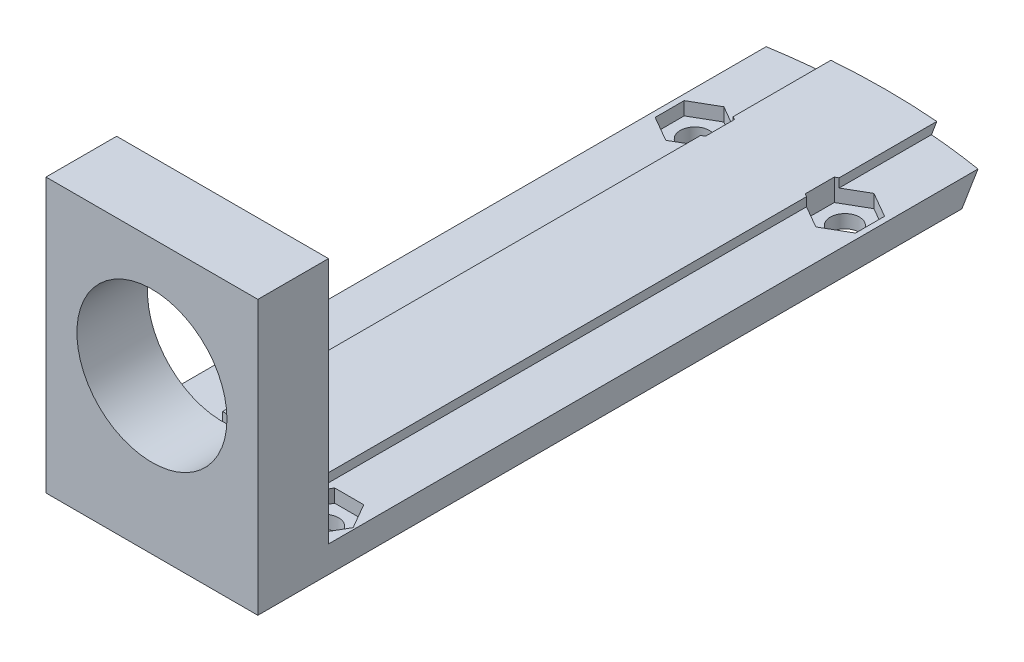
SolidWorks part; units mm, degrees
ref_plane "Front Plane" through (0, 0, 0) normal (0, 0, 1) x (1, 0, 0)
ref_plane "Top Plane" through (0, 0, 0) normal (0, 1, 0) x (1, 0, 0)
ref_plane "Right Plane" through (0, 0, 0) normal (1, 0, 0) x (0, 0, -1)
sketch "Sketch1" plane through (0, 0, 0) normal (0, 1, 0) x (1, 0, 0)
  line L1 (0, 0) -> (24, 0)
  line L2 (0, 0) -> (0, 81.5022)
  line L3 (0, 81.5022) -> (24, 81.5022)
  line L4 (24, 0) -> (24, 81.5022)
  dimension "D1" = 24
extrude "Boss-Extrude1" add sketch "Sketch1" along normal blind 3
sketch "Sketch2" plane through (0, 0, 0) normal (0, 1, 0) x (1, 0, 0)
  line L0 (0, 0) -> (24, 0) construction
  circle A0 centre (3.5, 3) radius 1.65
  circle A1 centre (12, 3) radius 1.65
  circle A2 centre (20.5, 3) radius 1.65
  circle A6 centre (3.5, 62) radius 1.65
  circle A8 centre (20.5, 62) radius 1.65
  circle A9 centre (12, 32.5) radius 1.65 [skipped]
  circle A10 centre (3.5, 32.5) radius 1.65 [skipped]
  circle A11 centre (20.5, 32.5) radius 1.65 [skipped]
  circle A12 centre (12, 62) radius 1.65 [skipped]
  point P9 (12, 0)
  dimension "D1" = 3.3
  dimension "D2" = 3
  dimension "D3" = 8.5
  dimension "D4" = 8.5
  dimension "D5" = 3
  dimension "D6" = 59
extrude "Cut-Extrude1" cut sketch "Sketch2" along normal through all
sketch "Sketch3" plane through (0, 0, 0) normal (0, 0, 1) x (1, 0, 0)
  line L0 (0, 3) -> (24, 3) construction
  line L1 (6, 3) -> (18, 3)
  line L2 (6, 3) -> (6, 4)
  line L3 (6, 4) -> (18, 4)
  line L4 (18, 3) -> (18, 4)
  line L5 (77.5014, 4) -> (-53.5014, 4) construction
  point P11 (12, 3)
  dimension "D1" = 12
  dimension "D2" = 12
extrude "Boss-Extrude2" add sketch "Sketch3" against normal up to surface (81.5022 mm away) from offset 6 up to face at (12, 1.5, -81.5022) offset against normal yes
ref_plane "Plane1" through (12, 0, 0) normal (-1, 0, 0) x (0, 0, 1)
sketch "Sketch4" plane through (12, 0, 0) normal (1, 0, 0) x (0, 0, -1)
  line L0 (94.4965, 36.2415) -> (19.4137, -88.8964)
  line L1 (19.4137, -88.8964) -> (139.5903, -88.8964)
  line L2 (139.5903, -88.8964) -> (139.5903, 36.2415)
  line L3 (139.5903, 36.2415) -> (94.4965, 36.2415)
  line L4 (73, -6) -> (79, 4) construction
  line L6 (0, 0) -> (0, 3) construction
  dimension "D1" = 3.3
revolve "Cut-Revolve1" cut sketch "Sketch4" angle 360 about L6
sketch "Sketch5" plane through (0, 3, 0) normal (0, 1, 0) x (1, 0, 0)
  line L0 (18, 74.3097) -> (18, 6) construction
  line L1 (15.2909, 3) -> (13.6454, 5.85)
  line L2 (13.6454, 5.85) -> (10.3546, 5.85)
  line L3 (10.3546, 5.85) -> (8.7091, 3)
  line L4 (8.7091, 3) -> (10.3546, 0.15)
  line L5 (10.3546, 0.15) -> (13.6454, 0.15)
  line L6 (13.6454, 0.15) -> (15.2909, 3)
  line L7 (23.7909, 3) -> (22.1454, 5.85)
  line L8 (22.1454, 5.85) -> (18.8546, 5.85)
  line L9 (18.8546, 5.85) -> (17.2091, 3)
  line L10 (17.2091, 3) -> (18.8546, 0.15)
  line L11 (18.8546, 0.15) -> (22.1454, 0.15)
  line L12 (22.1454, 0.15) -> (23.7909, 3)
  line L13 (6.7909, 3) -> (5.1454, 5.85)
  line L14 (5.1454, 5.85) -> (1.8546, 5.85)
  line L15 (1.8546, 5.85) -> (0.2091, 3)
  line L16 (0.2091, 3) -> (1.8546, 0.15)
  line L17 (1.8546, 0.15) -> (5.1454, 0.15)
  line L18 (5.1454, 0.15) -> (6.7909, 3)
  line L31 (6.35, 63.6454) -> (3.5, 65.2909)
  line L32 (3.5, 65.2909) -> (0.65, 63.6454)
  line L33 (0.65, 63.6454) -> (0.65, 60.3546)
  line L34 (0.65, 60.3546) -> (3.5, 58.7091)
  line L35 (3.5, 58.7091) -> (6.35, 60.3546)
  line L36 (6.35, 60.3546) -> (6.35, 63.6454)
  line L37 (23.35, 63.6454) -> (20.5, 65.2909)
  line L38 (20.5, 65.2909) -> (17.65, 63.6454)
  line L39 (17.65, 63.6454) -> (17.65, 60.3546)
  line L40 (17.65, 60.3546) -> (20.5, 58.7091)
  line L41 (20.5, 58.7091) -> (23.35, 60.3546)
  line L42 (23.35, 60.3546) -> (23.35, 63.6454)
  line L43 (6, 74.3097) -> (6, 6) construction
  circle A0 centre (12, 3) radius 2.85 construction
  circle A1 centre (20.5, 3) radius 2.85 construction
  circle A2 centre (3.5, 3) radius 2.85 construction
  circle A3 centre (3.5, 62) radius 2.85 construction
  circle A4 centre (20.5, 62) radius 2.85 construction
  dimension "D1" = 5.7
  dimension "D2" = 5.7
extrude "Cut-Extrude2" cut sketch "Sketch5" against normal blind 1.5 and the other way through all
sketch "Sketch6" plane through (0, 0, 0) normal (0, 0, 1) x (1, 0, 0)
  line L0 (12, 2.2) -> (12, -2.2) construction
  line L1 (0, 0) -> (24, 0)
  line L2 (0, 0) -> (0, 31)
  line L3 (0, 31) -> (24, 31)
  line L4 (24, 0) -> (24, 31)
  circle A0 centre (12, 17.5) radius 8.5
  dimension "D2" = 17
  dimension "D1" = 31
  dimension "D3" = 17.5
extrude "Boss-Extrude3" add sketch "Sketch6" along normal blind 8
